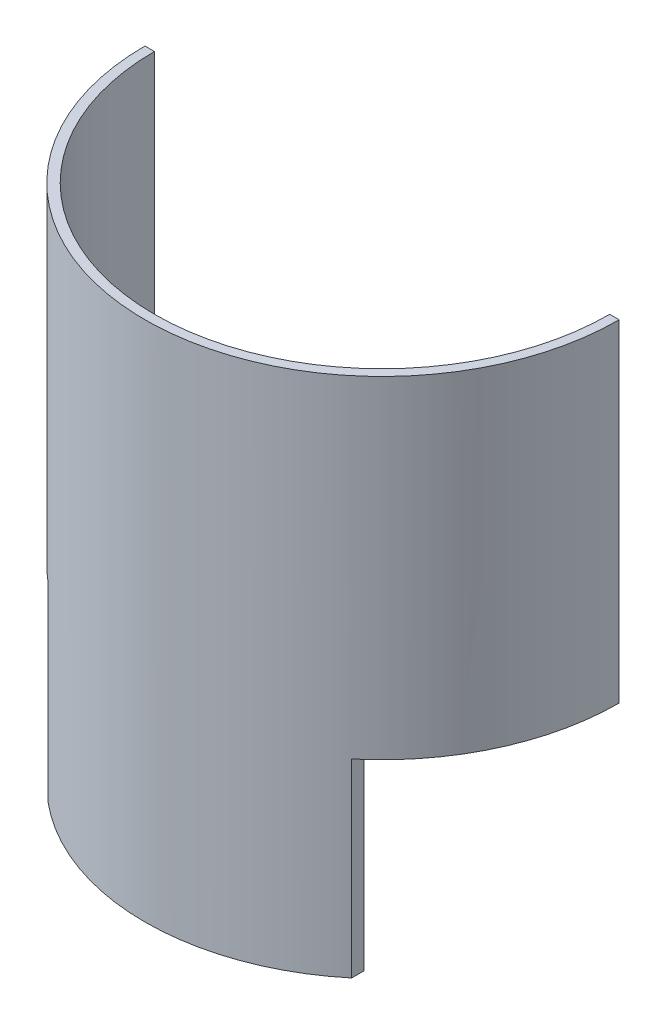
SolidWorks part; units mm, degrees
material "Rubber"
ref_plane "Front Plane" through (0, 0, 0) normal (0, 0, 1) x (1, 0, 0)
ref_plane "Top Plane" through (0, 0, 0) normal (0, 1, 0) x (1, 0, 0)
ref_plane "Right Plane" through (0, 0, 0) normal (1, 0, 0) x (0, 0, -1)
sketch "Sketch1" plane through (0, 0, 0) normal (0, 1, 0) x (1, 0, 0)
  line L0 (-12.5, 0) -> (-12, 0)
  line L1 (12, 0) -> (12.5, 0)
  line L2 (-8, -8.9443) -> (-8, -9.6047)
  line L3 (8, -8.9443) -> (8, -9.6047)
  arc A0 (-12.5, 0) -> (12.5, 0) centre (0, 0) ccw
  arc A1 (-12, 0) -> (12, 0) centre (0, 0) ccw
  dimension "D1" = 12.5
  dimension "D2" = 12
  dimension "D3" = 16
extrude "Boss-Extrude1" add sketch "Sketch1" along normal blind 10 contours A1 L2 A0 L3 region at (-7.8361, 0, 9.2745)
extrude "Boss-Extrude2" add sketch "Sketch1<3>" along normal blind 17.5 from offset 10 contours A1 L0 A0 L2 | A1 L2 A0 L3 | A1 L3 A0 L1 region at (-12.25, 0, 0.1061) region at (-7.8361, 0, 9.2745) region at (8.1061, 0, 9.2745)
sketch "Sketch1<3>" plane through (0, 0, 0) normal (0, 1, 0) x (1, 0, 0) same geometry as "Sketch1"
sketch "Sketch2" plane through (0, 0, 0) normal (0, -1, 0) x (1, 0, 0)
  line L0 (-8, 9.6047) -> (-8, 8.9443)
